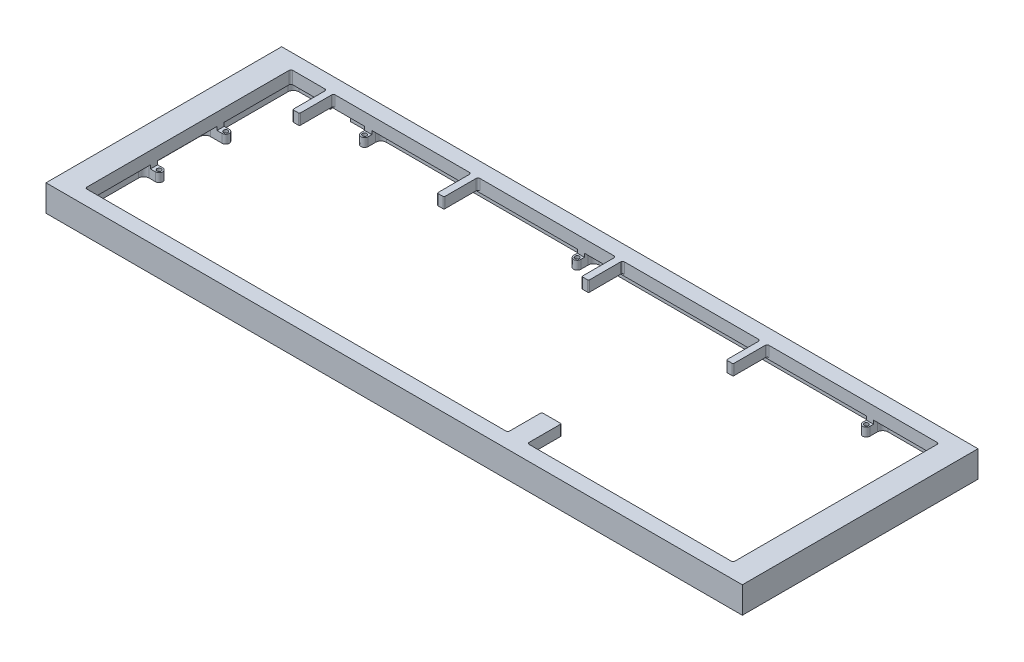
SolidWorks part; units mm, degrees
ref_plane "Front Plane" through (0, 0, 0) normal (0, 0, 1) x (1, 0, 0)
ref_plane "Top Plane" through (0, 0, 0) normal (0, 1, 0) x (1, 0, 0)
ref_plane "Right Plane" through (0, 0, 0) normal (1, 0, 0) x (0, 0, -1)
sketch "Sketch1" plane through (0, 0, 0) normal (0, 1, 0) x (1, 0, 0)
  line L1 (0, 0) -> (390, 0)
  line L2 (0, 0) -> (0, 132)
  line L3 (0, 132) -> (390, 132)
  line L4 (390, 0) -> (390, 132)
  dimension "D1" = 132
  dimension "D2" = 390
extrude "Boss-Extrude1" add sketch "Sketch1" along normal blind 14.8
sketch "Sketch2" plane through (0, 0, 0) normal (0, -1, 0) x (1, 0, 0)
  line L0 (390, -132) -> (0, -132) construction
  line L1 (388, -130) -> (2, -130)
  line L2 (388, -130) -> (388, -2)
  line L3 (388, -2) -> (2, -2)
  line L4 (2, -130) -> (2, -2)
  line L5 (390, 0) -> (390, -132) construction
  point P4 (195, -130)
  point P7 (195, -132)
  point P8 (388, -66)
  point P11 (390, -66)
  dimension "D1" = 2
  dimension "D2" = 2
extrude "Cut-Extrude1" cut sketch "Sketch2" against normal blind 1
sketch "Sketch3" plane through (0, 14.8, 0) normal (0, 1, 0) x (1, 0, 0)
  line L0 (16.55, 120.125) -> (16.55, 107.125) construction
  line L1 (13.55, 123.625) -> (376.45, 123.625)
  line L2 (13.55, 123.625) -> (13.55, 8.375)
  line L3 (13.55, 8.375) -> (376.45, 8.375)
  line L4 (376.45, 123.625) -> (376.45, 8.375)
  line L5 (0, 132) -> (0, 0) construction
  line L6 (390, 132) -> (0, 132) construction
  line L7 (17.05, 120.625) -> (30.05, 120.625) construction
  point P6 (13.55, 66)
  point P9 (0, 66)
  point P10 (195, 123.625)
  point P13 (195, 132)
  dimension "D1" = 3
  dimension "D2" = 3
extrude "Cut-Extrude2" cut sketch "Sketch3" against normal through all
sketch "Sketch4" plane through (0, 1, 0) normal (0, -1, 0) x (-1, 0, 0)
  line L0 (-388, 130) -> (-388, 2) construction
  line L1 (-380.15, 128.7375) -> (-9.85, 128.7375)
  line L2 (-380.15, 128.7375) -> (-380.15, 3.2625)
  line L3 (-380.15, 3.2625) -> (-9.85, 3.2625)
  line L4 (-9.85, 128.7375) -> (-9.85, 3.2625)
  line L6 (-13.55, 123.625) -> (-376.45, 123.625) construction
  line L7 (-379.15, 51.7125) -> (-379.15, 79.5255) construction
  line L9 (-333.1125, 124.7375) -> (-180.7125, 124.7375) construction
  point P4 (-380.15, 66)
  point P7 (-388, 66)
  point P12 (-195, 123.625)
  point P13 (-195, 128.7375)
  dimension "D1" = 1
  dimension "D2" = 4
extrude "Cut-Extrude3" cut sketch "Sketch4" against normal blind 6.8
sketch "Sketch5" plane through (0, 7.8, 0) normal (0, -1, 0) x (1, 0, 0)
  line L0 (13.55, -8.375) -> (376.45, -8.375) construction
  line L1 (380.15, -128.7375) -> (380.15, -3.2625) construction
  line L2 (373.5937, -48.95) -> (380.15, -48.95)
  line L3 (373.5937, -48.95) -> (373.5937, -44.95)
  line L4 (373.5937, -44.95) -> (380.15, -44.95)
  line L5 (380.15, -48.95) -> (380.15, -44.95)
  line L6 (380.15, -3.2625) -> (9.85, -3.2625) construction
  line L7 (301.775, -10.475) -> (297.775, -10.475)
  line L8 (301.775, -10.475) -> (301.775, -3.2625)
  line L9 (301.775, -3.2625) -> (297.775, -3.2625)
  line L10 (297.775, -10.475) -> (297.775, -3.2625)
  line L11 (9.85, -3.2625) -> (9.85, -128.7375) construction
  line L12 (87.4625, -10.475) -> (83.4625, -10.475)
  line L13 (87.4625, -10.475) -> (87.4625, -3.2625)
  line L14 (87.4625, -3.2625) -> (83.4625, -3.2625)
  line L15 (83.4625, -10.475) -> (83.4625, -3.2625)
  line L16 (16.4062, -48.95) -> (9.85, -48.95)
  line L17 (16.4062, -48.95) -> (16.4062, -44.95)
  line L18 (16.4062, -44.95) -> (9.85, -44.95)
  line L19 (9.85, -48.95) -> (9.85, -44.95)
  line L20 (9.85, -128.7375) -> (380.15, -128.7375) construction
  line L21 (16.4062, -86.2562) -> (9.85, -86.2562)
  line L22 (16.4062, -86.2562) -> (16.4062, -82.2562)
  line L23 (16.4062, -82.2562) -> (9.85, -82.2562)
  line L24 (9.85, -86.2562) -> (9.85, -82.2562)
  line L25 (58.8875, -121.5625) -> (54.8875, -121.5625)
  line L26 (58.8875, -121.5625) -> (58.8875, -128.7375)
  line L27 (58.8875, -128.7375) -> (54.8875, -128.7375)
  line L28 (54.8875, -121.5625) -> (54.8875, -128.7375)
  line L30 (177.95, -121.5625) -> (173.95, -121.5625)
  line L31 (177.95, -121.5625) -> (177.95, -128.7375)
  line L32 (177.95, -128.7375) -> (173.95, -128.7375)
  line L33 (173.95, -121.5625) -> (173.95, -128.7375)
  line L34 (339.875, -121.5625) -> (335.875, -121.5625)
  line L35 (339.875, -121.5625) -> (339.875, -128.7375)
  line L36 (339.875, -128.7375) -> (335.875, -128.7375)
  line L37 (335.875, -121.5625) -> (335.875, -128.7375)
  line L38 (373.5937, -86.288) -> (380.15, -86.288)
  line L39 (373.5937, -86.288) -> (373.5937, -82.288)
  line L40 (373.5937, -82.288) -> (380.15, -82.288)
  line L41 (380.15, -86.288) -> (380.15, -82.288)
  line L42 (380.15, -128.7375) -> (380.15, -3.2625) construction
  circle A0 centre (373.5937, -46.95) radius 2
  circle A1 centre (373.5937, -84.288) radius 2
  circle A2 centre (337.875, -121.5625) radius 2
  circle A3 centre (299.775, -10.475) radius 2
  circle A4 centre (85.4625, -10.475) radius 2
  circle A5 centre (16.4062, -46.95) radius 2
  circle A6 centre (175.95, -121.5625) radius 2
  circle A7 centre (56.8875, -121.5625) radius 2
  circle A8 centre (16.4062, -84.2562) radius 2
  arc A9 (16.4062, -86.6375) -> (16.4062, -81.875) centre (16.4062, -84.2562) ccw construction
  arc A10 (16.4062, -49.3312) -> (16.4062, -44.5687) centre (16.4062, -46.95) ccw construction
  arc A11 (59.2687, -121.5625) -> (54.5062, -121.5625) centre (56.8875, -121.5625) ccw construction
  arc A12 (178.3312, -121.5625) -> (173.5687, -121.5625) centre (175.95, -121.5625) ccw construction
  arc A13 (340.2562, -121.5625) -> (335.4937, -121.5625) centre (337.875, -121.5625) ccw construction
  arc A14 (373.5937, -81.9067) -> (373.5937, -86.6692) centre (373.5937, -84.288) ccw construction
  arc A15 (373.5937, -44.5687) -> (373.5937, -49.3312) centre (373.5937, -46.95) ccw construction
  arc A16 (297.3938, -11.2312) -> (302.1562, -11.2312) centre (299.775, -11.2312) ccw construction
  arc A17 (83.0812, -11.2312) -> (87.8437, -11.2312) centre (85.4625, -11.2312) ccw construction
  point P47 (299.775, -13.6125)
  point P52 (85.4625, -13.6125)
  dimension "D2" = 4
  dimension "D1" = 2.1
extrude "Boss-Extrude2" add sketch "Sketch5" along normal up to surface (6.8 mm away) contours L40 L41 L38 L39 | A1 | L4 L5 L2 L3 | A0 | A3 | L8 L9 L10 L7 | L35 L36 L37 L34 | A2 | L33 L32 L31 L30 | A6 | L28 L27 L26 L25 | A7 | L16 L19 L18 L17 | A5 | A8 | L21 L24 L23 L22 | L15 L14 L13 L12 | A4 up to face at (195, 1, -66)
sketch "Sketch6" plane through (0, 7.8, 0) normal (0, 1, 0) x (1, 0, 0)
  line L1 (13.55, 123.625) -> (376.45, 123.625)
  line L2 (13.55, 123.625) -> (13.55, 8.375)
  line L3 (13.55, 8.375) -> (376.45, 8.375)
  line L4 (376.45, 123.625) -> (376.45, 8.375)
extrude "Cut-Extrude4" cut sketch "Sketch6" against normal blind 2
sketch "Sketch7" plane through (0, 1, 0) normal (0, -1, 0) x (-1, 0, 0)
  line L1 (-380.15, 82.288) -> (-383.15, 82.288)
  line L2 (-380.15, 82.288) -> (-380.15, 48.95)
  line L3 (-380.15, 48.95) -> (-383.15, 48.95)
  line L4 (-383.15, 82.288) -> (-383.15, 48.95)
  line L5 (-9.85, 82.2562) -> (-6.85, 82.2562)
  line L6 (-9.85, 82.2562) -> (-9.85, 48.95)
  line L7 (-9.85, 48.95) -> (-6.85, 48.95)
  line L8 (-6.85, 82.2562) -> (-6.85, 48.95)
  line L9 (-16.4062, 48.95) -> (-9.85, 48.95) construction
  line L10 (-373.5937, 48.95) -> (-380.15, 48.95) construction
  dimension "D1" = 3
extrude "Cut-Extrude5" cut sketch "Sketch7" against normal up to surface (6.8 mm away) up to face at (11.7, 7.8, -65.6031)
sketch "Sketch8" plane through (0, 7.8, 0) normal (0, -1, 0) x (-1, 0, 0)
  point P0 (-359.7125, 126.7375)
  point P1 (-381.15, 65.619)
  point P3 (-359.7125, 5.2625)
  point P5 (-241.0375, 5.2625)
  point P7 (-148.9625, 5.2625)
  point P9 (-32.6687, 5.2625)
  point P11 (-8.85, 65.619)
  point P13 (-26.85, 126.7375)
  point P15 (-102.925, 126.7375)
  point P17 (-195, 126.7375)
  point P19 (-287.075, 126.7375)
  point P21 (0, 0)
  point P23 (-32.6687, 126.7375)
  point P24 (0, 0)
  point P25 (-32.6687, 126.7375)
hole_wizard "M2x0.4 Tapped Hole1" positions "3DSketch1" profile "Sketch9" tap size "M2x0.4" standard "ANSI Metric"
sketch3d "3DSketch1"
  point P0 (359.7125, 7.8, -126.7375)
  point P3 (381.15, 7.8, -65.619)
  point P6 (359.7125, 7.8, -5.2625)
  point P9 (241.0375, 7.8, -5.2625)
  point P12 (287.075, 7.8, -126.7375)
  point P15 (195, 7.8, -126.7375)
  point P18 (148.9625, 7.8, -5.2625)
  point P21 (102.925, 7.8, -126.7375)
  point P24 (26.85, 7.8, -126.7375)
  point P27 (8.85, 7.8, -65.619)
  point P30 (32.6687, 7.8, -5.2625)
sketch "Sketch9" plane through (359.7125, 7.8, -126.7375) normal (1, 0, 0) x (0, 0, -1)
  line L0 (0, 0) -> (0, 4.4807)
  line L1 (0, 4.4807) -> (0.8, 4)
  line L2 (0.8, 4) -> (0.8, 0)
  line L5 (0.8, 0) -> (0, 0)
  line L10 (0, 4.4807) -> (-0.8, 4) construction
  line L11 (0, -6.35) -> (0, 107.95) construction
  dimension "Tap Drill Dia." = 1.6
  dimension "Tap Drill Depth" = 4
  dimension "Drill Angle" = 118
cosmetic thread "Hole Thread1" parameters "D1"=4, "D2"=2
cosmetic thread "Hole Thread2" parameters "D1"=4, "D2"=2
cosmetic thread "Hole Thread3" parameters "D1"=4, "D2"=2
cosmetic thread "Hole Thread4" parameters "D1"=4, "D2"=2
cosmetic thread "Hole Thread5" parameters "D1"=4, "D2"=2
cosmetic thread "Hole Thread6" parameters "D1"=4, "D2"=2
cosmetic thread "Hole Thread7" parameters "D1"=4, "D2"=2
cosmetic thread "Hole Thread8" parameters "D1"=4, "D2"=2
cosmetic thread "Hole Thread9" parameters "D1"=4, "D2"=2
cosmetic thread "Hole Thread10" parameters "D1"=4, "D2"=2
cosmetic thread "Hole Thread11" parameters "D1"=4, "D2"=2
sketch "Sketch10" plane through (0, 0, -132) normal (0, 0, -1) x (-1, 0, 0)
  line L0 (-390, 0) -> (0, 0) construction
  line L1 (-41.7062, 0) -> (-29.2062, 0)
  line L2 (-41.7062, 0) -> (-41.7062, 2.8)
  line L3 (-41.7062, 2.8) -> (-29.2062, 2.8)
  line L4 (-29.2062, 0) -> (-29.2062, 2.8)
  line L5 (-32.3112, -1.685) -> (-38.6012, -1.685) construction
  line L6 (-41.1458, 2.8) -> (-41.1395, 2.8) construction
  point P6 (-35.4562, 0)
  point P9 (-35.4562, -1.685)
  dimension "D1" = 12.5
extrude "Cut-Extrude6" cut sketch "Sketch10" against normal blind 10
sketch "Sketch11" plane through (0, 2.8, 0) normal (0, -1, 0) x (1, 0, 0)
  line L0 (29.2062, -128.7375) -> (41.7062, -128.7375) construction
  line L1 (41.7062, -128.7375) -> (29.2062, -128.7375)
  line L2 (41.7062, -128.7375) -> (41.7062, -129.7375)
  line L3 (41.7062, -129.7375) -> (29.2062, -129.7375)
  line L4 (29.2062, -128.7375) -> (29.2062, -129.7375)
  line L5 (29.2062, -132) -> (41.7062, -132) construction
  point P6 (35.4562, -129.7375)
  point P9 (35.4562, -132)
  dimension "D1" = 12.5
  dimension "D2" = 1
extrude "Cut-Extrude7" cut sketch "Sketch11" against normal blind 1
sketch "Sketch12" plane through (0, 5.8, 0) normal (0, 1, 0) x (1, 0, 0)
  point P0 (16.4062, 84.2562)
  point P1 (16.4062, 46.95)
  point P3 (85.4625, 10.475)
  point P5 (299.775, 10.475)
  point P7 (373.5937, 46.95)
  point P9 (373.5937, 84.288)
  point P11 (337.875, 121.5625)
  point P13 (175.95, 121.5625)
  point P15 (56.8875, 121.5625)
  point P17 (16.4062, 84.288)
hole_wizard "M2 Clearance Hole1" positions "3DSketch2" profile "Sketch13" hole size "M2" standard "ANSI Metric" end condition through all
sketch3d "3DSketch2"
  point P0 (16.4062, 5.8, -46.95)
  point P3 (16.4062, 5.8, -84.2562)
  point P6 (56.8875, 5.8, -121.5625)
  point P9 (85.4625, 5.8, -10.475)
  point P12 (175.95, 5.8, -121.5625)
  point P15 (299.775, 5.8, -10.475)
  point P18 (373.5937, 5.8, -46.95)
  point P21 (373.5937, 5.8, -84.288)
  point P24 (337.875, 5.8, -121.5625)
sketch "Sketch13" plane through (16.4062, 5.8, -46.95) normal (1, 0, 0) x (0, 0, 1)
  line L0 (0, 0) -> (0, 5.8)
  line L1 (0, 5.8) -> (1.2, 5.8)
  line L2 (1.2, 5.8) -> (1.2, 0)
  line L5 (1.2, 0) -> (0, 0)
  line L11 (0, -6.35) -> (0, 107.95) construction
  dimension "Thru Hole Dia." = 2.4
  dimension "Thru Hole Depth" = 5.8
fillet "Fillet1" radius 3 24 edges at (380.15, 4.4, -3.2625) (9.85, 4.4, -3.2625) (29.2062, 3.3, -129.7375) (41.7062, 3.3, -129.7375) (177.95, 4.4, -128.7375) (173.95, 4.4, -128.7375) (54.8875, 4.4, -128.7375) (58.8875, 4.4, -128.7375) (9.85, 4.4, -128.7375) (9.85, 4.4, -86.2562) (6.85, 4.4, -82.2562) (6.85, 4.4, -48.95) (9.85, 4.4, -44.95) (87.4625, 4.4, -3.2625) (83.4625, 4.4, -3.2625) (297.775, 4.4, -3.2625) (301.775, 4.4, -3.2625) (380.15, 4.4, -44.95) (383.15, 4.4, -48.95) (380.15, 4.4, -86.288) (383.15, 4.4, -82.288) (380.15, 4.4, -128.7375) (335.875, 4.4, -128.7375) (339.875, 4.4, -128.7375)
fillet "Fillet2" radius 4 4 edges at (2, 0.5, -2) (2, 0.5, -130) (388, 0.5, -130) (388, 0.5, -2)
sketch "Sketch14" plane through (0, 14.8, 0) normal (0, 1, 0) x (1, 0, 0)
  line L0 (376.45, 123.625) -> (13.55, 123.625) construction
  line L1 (33.55, 123.625) -> (37.3625, 123.625)
  line L2 (33.55, 123.625) -> (33.55, 104.575)
  line L3 (33.55, 104.575) -> (37.3625, 104.575)
  line L4 (37.3625, 123.625) -> (37.3625, 104.575)
  line L5 (13.55, 8.375) -> (376.45, 8.375) construction
  line L6 (114.5125, 123.625) -> (118.325, 123.625)
  line L7 (114.5125, 123.625) -> (114.5125, 104.575)
  line L8 (114.5125, 104.575) -> (118.325, 104.575)
  line L9 (118.325, 123.625) -> (118.325, 104.575)
  line L14 (276.4375, 123.625) -> (280.25, 123.625)
  line L15 (276.4375, 123.625) -> (276.4375, 104.575)
  line L16 (276.4375, 104.575) -> (280.25, 104.575)
  line L17 (280.25, 123.625) -> (280.25, 104.575)
  line L18 (250.2437, 8.375) -> (261.2, 8.375)
  line L19 (250.2437, 8.375) -> (250.2437, 27.425)
  line L20 (250.2437, 27.425) -> (261.2, 27.425)
  line L21 (261.2, 8.375) -> (261.2, 27.425)
  line L22 (36.1, 101.575) -> (49.1, 101.575) construction
  line L23 (231.3625, 30.425) -> (244.3625, 30.425) construction
  line L24 (30.55, 120.125) -> (30.55, 107.125) construction
  line L25 (40.3625, 120.125) -> (40.3625, 107.125) construction
  line L26 (111.5125, 120.125) -> (111.5125, 107.125) construction
  line L27 (121.325, 120.125) -> (121.325, 107.125) construction
  line L28 (192.475, 120.125) -> (192.475, 107.125) construction
  line L29 (195.475, 123.625) -> (199.2875, 123.625)
  line L30 (195.475, 123.625) -> (195.475, 104.575)
  line L31 (195.475, 104.575) -> (199.2875, 104.575)
  line L32 (199.2875, 123.625) -> (199.2875, 104.575)
  line L33 (202.2875, 120.125) -> (202.2875, 107.125) construction
  line L34 (273.4375, 120.125) -> (273.4375, 107.125) construction
  line L35 (283.25, 120.125) -> (283.25, 107.125) construction
  line L36 (264.2, 24.875) -> (264.2, 11.875) construction
  line L37 (247.2437, 24.875) -> (247.2437, 11.875) construction
  point P30 (30.55, 113.625)
  point P47 (264.2, 18.375)
  dimension "D1" = 3
  dimension "D2" = 3
  dimension "D3" = 3
  dimension "D4" = 3
  dimension "D5" = 3
  dimension "D6" = 3
  dimension "D7" = 3
  dimension "D8" = 3
  dimension "D9" = 3
  dimension "D10" = 3
  dimension "D11" = 3
  dimension "D12" = 3
extrude "Boss-Extrude4" add sketch "Sketch14" against normal offset from surface (6 mm away) 1 up to face at (8.85, 7.8, -66.419)
fillet "Fillet3" radius 1 14 edges at (376.45, 11.3, -123.625) (376.45, 11.3, -8.375) (13.55, 11.3, -8.375) (13.55, 11.3, -123.625) (261.2, 11.8, -8.375) (250.2437, 11.8, -8.375) (276.4375, 11.8, -123.625) (280.25, 11.8, -123.625) (199.2875, 11.8, -123.625) (195.475, 11.8, -123.625) (118.325, 11.8, -123.625) (114.5125, 11.8, -123.625) (37.3625, 11.8, -123.625) (33.55, 11.8, -123.625)
fillet "Fillet4" radius 0.5 10 edges at (250.2437, 11.8, -27.425) (261.2, 11.8, -27.425) (276.4375, 11.8, -104.575) (280.25, 11.8, -104.575) (195.475, 11.8, -104.575) (199.2875, 11.8, -104.575) (114.5125, 11.8, -104.575) (118.325, 11.8, -104.575) (37.3625, 11.8, -104.575) (33.55, 11.8, -104.575)
